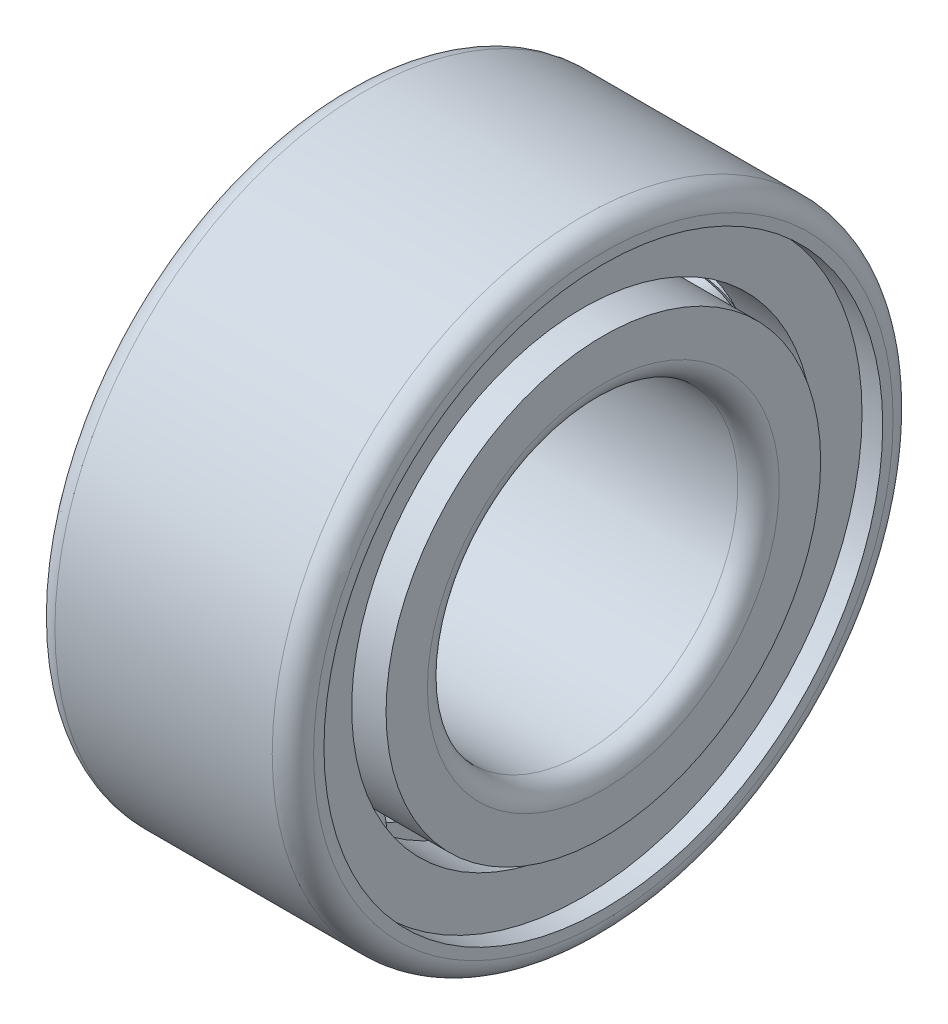
SolidWorks part; units mm, degrees
revolve "凸台-旋转2" add sketch "草图6" angle 360 about L4
sketch "草图6" plane through (0, 0, 0) normal (0, 0, 1) x (1, 0, 0)
  line L0 (0, 0) -> (5.5439, 0) construction
  line L1 (-12.4206, 0) -> (9.8128, 0) construction
  line L2 (0, 0) -> (0, 11.4011) construction
  line L3 (-5.5681, 2.4) -> (6.1049, 2.4) construction
  line L4 (-5.5681, 2.4) -> (6.1049, 2.4) construction
  line L5 (-0.4, 2.4) -> (0.4, 2.4)
  arc A0 (-0.4, 2.4) -> (0.4, 2.4) centre (0, 2.4) ccw
  dimension "Dw" = 0.8
revolve "基体-旋转" add sketch "草图2" angle 360 about L0
sketch "草图2" plane through (0, 0, 0) normal (0, 0, 1) x (1, 0, 0)
  line L0 (-12.4206, 0) -> (9.8128, 0) construction
  line L1 (0, 0) -> (0, 37.3563) construction
  line L2 (-5.5681, 2.4) -> (6.1049, 2.4) construction
  line L3 (-0.088, 2.51) -> (0.088, 2.51)
  line L4 (-0.088, 2.51) -> (-0.088, 2.29)
  line L5 (-0.088, 2.29) -> (0.088, 2.29)
  line L6 (0.088, 2.51) -> (0.088, 2.29)
  dimension "D1" = 0.176
  dimension "D2" = 0.088
  dimension "D3" = 0.22
  dimension "D4" = 0.11
  dimension "D5" = 2.4
revolve "凸台-旋转1" add sketch "草图3" angle 360 about L1
sketch "草图3" plane through (0, 0, 0) normal (0, 0, 1) x (1, 0, 0)
  line L0 (-5.5681, 2.4) -> (6.1049, 2.4) construction
  line L1 (-5.5681, 2.4) -> (6.1049, 2.4) construction
  line L2 (-12.4206, 0) -> (9.8128, 0) construction
  line L3 (-12.4206, 0) -> (9.8128, 0) construction
  line L4 (0, 0) -> (0, 37.3563) construction
  line L5 (0, 0) -> (0, 37.3563) construction
  line L6 (-0.44, 2.4) -> (0.44, 2.4)
  arc A0 (-0.44, 2.4) -> (0.44, 2.4) centre (0, 2.4) ccw
  dimension "Dwww" = 0.88
  dimension "D2" = 0.44
pattern_circular "阵列(圆周)1" count 10 over 360 about axis through (-12.4206, 0, 0) along (1, 0, 0) of "凸台-旋转1"
revolve "凸台-旋转3" add sketch "草图7" angle 360 about L0
sketch "草图7" plane through (0, 0, 0) normal (0, 0, 1) x (1, 0, 0)
  line L0 (0, 0) -> (6.6488, 0) construction
  line L1 (0, 0) -> (0, 16.8954) construction
  line L2 (-1.05, 3) -> (1.05, 3)
  line L3 (-1.25, 2.8) -> (-1.25, 2.7)
  line L4 (-1.25, 2.7) -> (-0.2492, 2.7)
  line L5 (1.25, 2.8) -> (1.25, 2.7)
  line L6 (0.2492, 2.7) -> (0.5148, 2.7)
  line L7 (1.05, 2.7) -> (1.25, 2.7)
  line L8 (0.5148, 2.6) -> (1.05, 2.6)
  line L9 (0.5148, 2.6) -> (0.5148, 2.7)
  line L11 (1.05, 2.6) -> (1.05, 2.7)
  arc A0 (-1.05, 3) -> (-1.25, 2.8) centre (-1.05, 2.8) ccw
  arc A1 (1.05, 3) -> (1.25, 2.8) centre (1.05, 2.8) cw
  arc A2 (0.3846, 2.51) -> (-0.3846, 2.51) centre (0, 2.4) ccw construction
  arc A3 (0.2646, 2.7) -> (0, 2.8) centre (0, 2.4) ccw construction
  arc A4 (0.2492, 2.7) -> (-0.2492, 2.7) centre (0, 2.4) ccw
  point P10 (-1.25, 3)
  point P13 (1.25, 3)
  dimension "D3" = 1.25
  dimension "D4" = 0.5352
  dimension "D5" = 5.2
  dimension "D6" = 0.2
  dimension "B" = 2.5
ref_plane "基准面1" through (0, 0, 0) normal (0, 0, 1) x (1, 0, 0)
ref_plane "基准面2" through (0, 0, 0) normal (0, 1, 0) x (1, 0, 0)
ref_plane "基准面3" through (0, 0, 0) normal (1, 0, 0) x (0, 0, -1)
sketch "尺寸草图" plane through (0, 0, 0) normal (0, 0, 1) x (1, 0, 0)
  point P0 (0, -75.4307)
  point P1 (0.8, -75.4307)
  point P2 (0, 50.7088)
  point P3 (3, 50.7088)
  point P4 (6, 50.7088)
  point P5 (2.5, 50.7088)
  point P6 (0, -10.9899)
  point P7 (4.2, -10.9899)
  point P8 (5.2, -10.9899)
  point P9 (0.2, -10.9899)
  point P10 (10, -75.4307)
  dimension "B" = 2.5
sketch "草图4" plane through (0, 0, 0) normal (0, 0, 1) x (1, 0, 0)
  line L0 (0, 0) -> (8.1272, 0) construction
  line L1 (-12.4206, 0) -> (9.8128, 0) construction
  line L3 (-0.088, 2.51) -> (0.088, 2.51) construction
  line L4 (-0.44, 2.95) -> (0.44, 2.95)
  line L5 (-0.44, 2.95) -> (-0.44, 2.51)
  line L6 (-0.44, 2.51) -> (0.44, 2.51)
  line L7 (0.44, 2.95) -> (0.44, 2.51)
revolve "切除-旋转1" cut sketch "草图4" angle 360 about L0
sketch "草图5" plane through (0, 0, 0) normal (0, 0, 1) x (1, 0, 0)
  line L0 (0, 0) -> (8.2665, 0) construction
  line L1 (-12.4206, 0) -> (9.8128, 0) construction
  line L2 (-0.088, 2.29) -> (0.088, 2.29) construction
  line L3 (-0.44, 2.29) -> (0.44, 2.29)
  line L4 (-0.44, 2.29) -> (-0.44, 1.85)
  line L5 (-0.44, 1.85) -> (0.44, 1.85)
  line L6 (0.44, 2.29) -> (0.44, 1.85)
revolve "切除-旋转2" cut sketch "草图5" angle 360 about L0
pattern_circular "阵列(圆周)2" count 10 over 360 about axis through (-12.4206, 0, 0) along (1, 0, 0) of "凸台-旋转2"
sketch "草图8" plane through (0, 0, 0) normal (0, 0, 1) x (1, 0, 0)
  line L0 (-12.4206, 0) -> (9.8128, 0) construction
  line L1 (-12.4206, 0) -> (9.8128, 0) construction
  line L2 (1.25, 2.8) -> (1.25, 2.7) construction
  line L3 (-1.25, 2.1) -> (-0.2492, 2.1)
  line L4 (-1.25, 2.1) -> (-1.25, 1.7)
  line L5 (-1.05, 1.5) -> (1.05, 1.5)
  line L6 (1.25, 2.1) -> (1.25, 1.7)
  line L7 (-1.25, 2.8) -> (-1.25, 2.7) construction
  line L8 (0.2492, 2.1) -> (1.25, 2.1)
  arc A0 (-1.25, 1.7) -> (-1.05, 1.5) centre (-1.05, 1.7) ccw
  arc A1 (1.05, 1.5) -> (1.25, 1.7) centre (1.05, 1.7) ccw
  arc A2 (-0.3846, 2.29) -> (0.3846, 2.29) centre (0, 2.4) ccw construction
  arc A3 (-0.3846, 2.29) -> (0.3846, 2.29) centre (0, 2.4) ccw construction
  arc A4 (-0.2492, 2.1) -> (0.2492, 2.1) centre (0, 2.4) ccw
  dimension "D1" = 0.2
  dimension "DD" = 3
  dimension "D2" = 0.01
revolve "凸台-旋转4" add sketch "草图8" angle 360 about L1
sketch "草图10" plane through (0, 0, 0) normal (0, 0, 1) x (1, 0, 0)
  line L0 (0.5148, 2.7) -> (0.5148, -2.7) construction
  line L1 (1.05, 2.6) -> (0.5148, 2.6)
  line L2 (1.05, 2.6) -> (1.05, 2.232)
  line L3 (1.05, 2.232) -> (0.5148, 2.232)
  line L4 (0.5148, 2.6) -> (0.5148, 2.232)
  line L5 (0.2492, 2.1) -> (1.25, 2.1) construction
  line L6 (0, 0) -> (-5.3515, 0) construction
  line L7 (-12.4206, 0) -> (9.8128, 0) construction
  dimension "D1" = 0.132
revolve "凸台-旋转5" add sketch "草图10" angle 360 about L6
sketch "草图11" plane through (0, 0, 0) normal (1, 0, 0) x (0, 0, -1)
  circle A0 centre (0, 0) radius 3
  circle A1 centre (0, 0) radius 3 construction
extrude "切除-拉伸1" cut sketch "草图11" against normal blind 10
mirror "镜向所有1" about plane through (0, 0, 0) normal (1, 0, 0) of bodies 109
equation "\"D5@草图7\" = \"防尘圈径D3@尺寸草图\""
equation "\"Z@阵列(圆周)1\"=\"球数Z@尺寸草图\" "
equation "\"Dw@草图6\"=\"球径DW@尺寸草图\""
equation "\"DD@草图8\"=\"d@尺寸草图\""
equation "\"D@草图7\"=\"DD@尺寸草图\""
equation "\"B@草图7\"=\"B@尺寸草图\" "
equation "\"DD2@草图8\"=\"内圈外径DD2@尺寸草图\""
equation "\"R@草图7\"=\"r@尺寸草图\""
equation "\"D3@草图2\" = 0.25*\"Dwww@草图3\""
equation "\"D4@草图2\" = \"D3@草图2\"/2"
equation "\"Dwww@草图3\" = 1.1*\"Dw@草图6\""
equation "\"D2@草图3\" = 0.5*\"Dwww@草图3\""
equation "\"D1@草图2\" = 0.2*\"Dwww@草图3\""
equation "\"D2@草图2\" = 0.5*\"D1@草图2\""
equation "\"切除位置@草图4\" = \"Dwww@草图3\"/2"
equation "\"D1@阵列(圆周)2\" = \"Z@阵列(圆周)1\""
equation "\"D3@草图7\" = \"B@草图7\" / 2"
equation "\"D1@草图8\" = \"R@草图7\""
equation "\"D2@草图7\" = 0.9*\"D@草图7\""
equation "\"D5@草图2\" = 0.25* ( \"D2@草图7\" + \"DD2@草图8\" )  "
equation "\"D6@草图7\" = 0.08 * \"B@草图7\""
equation "\"D1@草图10\" = 0.15*\"Dwww@草图3\""
